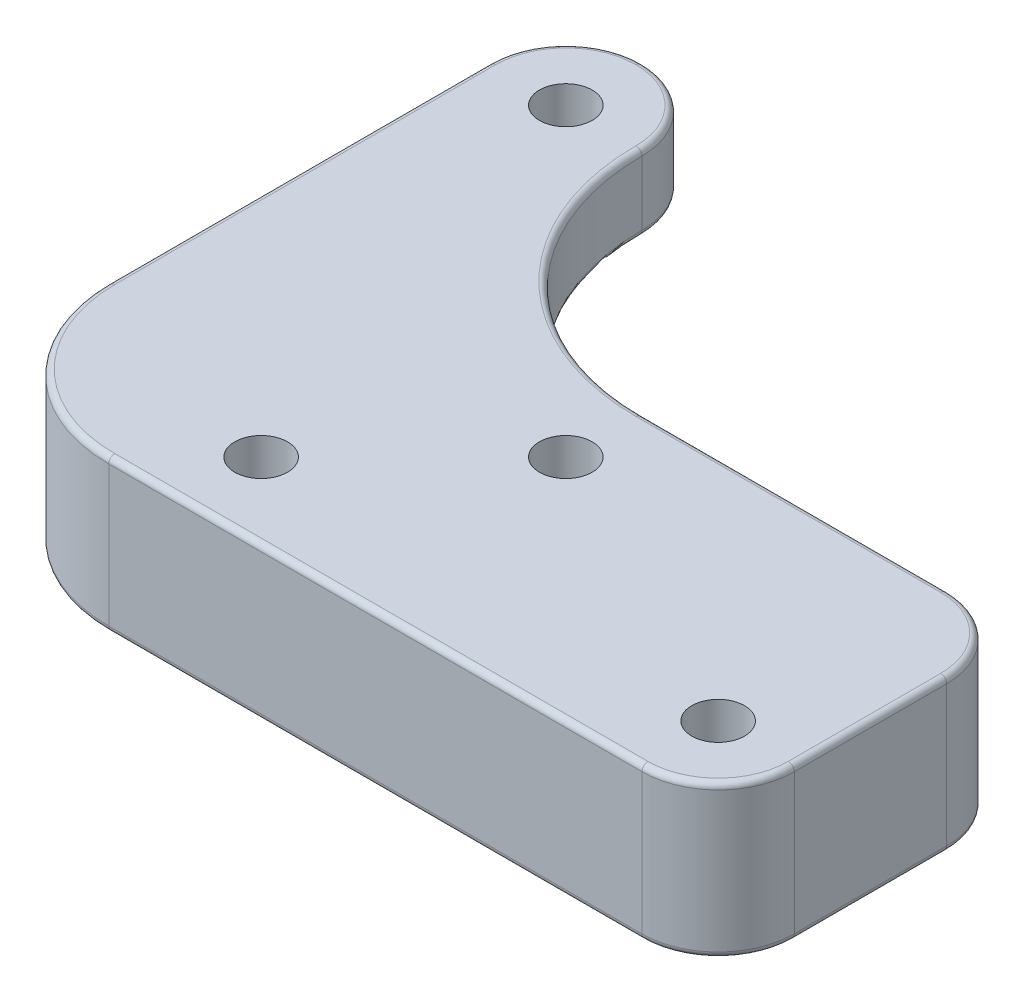
SolidWorks part; units mm, degrees
ref_plane "Front Plane" through (0, 0, 0) normal (0, 0, 1) x (1, 0, 0)
ref_plane "Top Plane" through (0, 0, 0) normal (0, 1, 0) x (1, 0, 0)
ref_plane "Right Plane" through (0, 0, 0) normal (1, 0, 0) x (0, 0, -1)
sketch "Sketch1" plane through (0, 0, 0) normal (0, 1, 0) x (1, 0, 0)
  line L0 (0, 0) -> (0, -50.8)
  line L2 (0, -50.8) -> (63.5, -50.8)
  line L3 (63.5, -50.8) -> (63.5, -25.4)
  line L4 (63.5, -25.4) -> (12.7, 0)
  line L5 (12.7, 0) -> (0, 0)
  line L6 (63.5, -25.4) -> (12.7, -25.4)
  line L7 (12.7, -25.4) -> (12.7, 0)
  circle A0 centre (19.05, -44.45) radius 2.2
  circle A1 centre (57.15, -44.45) radius 2.2
  circle A2 centre (31.75, -31.75) radius 2.2
  circle A3 centre (6.35, -6.35) radius 2.2
  point P14 (6.35, 0)
  point P15 (16.1819, -44.45)
  dimension "D1" = 4.4
  dimension "D2" = 25.4
  dimension "D3" = 12.7
  dimension "D4" = 25.4
  dimension "D5" = 63.5
  dimension "D6" = 6.35
  dimension "D7" = 6.35
  dimension "D8" = 6.35
  dimension "D9" = 12.7
  dimension "D10" = 12.7
  dimension "D11" = 12.7
extrude "Boss-Extrude1" add sketch "Sketch1" along normal blind 6.35 contours L6 L7 L5 L0 L2 L3 A3 A2 A1 A0
fillet "Fillet3" radius 19.05 1 edges at (12.7, 3.175, 25.4)
fillet "Fillet4" radius 6.35 2 edges at (0, 3.175, 0) (12.7, 3.175, 0)
fillet "Fillet5" radius 6.35 2 edges at (63.5, 3.175, 50.8) (63.5, 3.175, 25.4)
fillet "Fillet10" radius 12.7 1 edges at (0, 3.175, 50.8)
sketch "Sketch3" plane through (0, 0, 0) normal (0, -1, 0) x (1, 0, 0)
  line L0 (31.75, 25.4) -> (0, 25.4)
  line L4 (57.15, 50.8) -> (12.7, 50.8)
  line L5 (0, 38.1) -> (0, 6.35)
  line L6 (31.75, 25.4) -> (57.15, 25.4)
  line L7 (63.5, 31.75) -> (63.5, 44.45)
  line L8 (57.15, 50.8) -> (12.7, 50.8)
  line L9 (0, 38.1) -> (0, 6.35)
  line L10 (31.75, 25.4) -> (57.15, 25.4)
  line L11 (63.5, 31.75) -> (63.5, 44.45)
  circle A0 centre (57.15, 44.45) radius 2.2 construction
  circle A1 centre (19.05, 44.45) radius 2.2 construction
  circle A2 centre (31.75, 31.75) radius 2.2 construction
  circle A3 centre (57.15, 44.45) radius 2.2
  circle A4 centre (19.05, 44.45) radius 2.2
  circle A5 centre (31.75, 31.75) radius 2.2
  arc A7 (0, 6.35) -> (6.35, 0) centre (6.35, 6.35) ccw
  arc A8 (6.35, 0) -> (12.7, 6.35) centre (6.35, 6.35) ccw
  arc A9 (31.75, 25.4) -> (12.7, 6.35) centre (31.75, 6.35) ccw
  arc A10 (57.15, 25.4) -> (63.5, 31.75) centre (57.15, 31.75) ccw
  arc A11 (63.5, 44.45) -> (57.15, 50.8) centre (57.15, 44.45) ccw
  arc A13 (0, 6.35) -> (6.35, 0) centre (6.35, 6.35) ccw
  arc A14 (6.35, 0) -> (12.7, 6.35) centre (6.35, 6.35) ccw
  arc A15 (31.75, 25.4) -> (12.7, 6.35) centre (31.75, 6.35) ccw
  arc A16 (57.15, 25.4) -> (63.5, 31.75) centre (57.15, 31.75) ccw
  arc A17 (63.5, 44.45) -> (57.15, 50.8) centre (57.15, 44.45) ccw
  arc A23 (12.7, 50.8) -> (0, 38.1) centre (12.7, 38.1) ccw
  arc A24 (12.7, 50.8) -> (0, 38.1) centre (12.7, 38.1) ccw
  point P3 (0, 0)
  dimension "D1" = 0
extrude "Boss-Extrude3" add sketch "Sketch3" along normal blind 6.35
fillet "Fillet6" radius 12.7 1 edges at (0, -3.175, 25.4)
fillet "Fillet8" radius 3.175 2 edges at (3.7197, 0, 29.1197) (22.225, 0, 25.4)
fillet "Fillet9" radius 0.5 23 edges at (3.7197, -6.35, 29.1197) (0, -0.705, 32.4994) (24.0128, -0.3946, 23.758) (14.9645, 0, 15.3583) (18.2796, 6.35, 19.8204) (0, 0, 17.4625) (1.8599, 0, 1.8599) (10.8401, 0, 1.8599) (0, 6.35, 22.225) (1.8599, 6.35, 1.8599) (10.8401, 6.35, 1.8599) (63.5, 6.35, 38.1) (44.45, 6.35, 25.4) (61.6401, 6.35, 27.2599) (61.6401, 6.35, 48.9401) (34.925, 6.35, 50.8) (3.7197, 6.35, 47.0803) (34.925, -6.35, 25.4) (61.6401, -6.35, 27.2599) (63.5, -6.35, 38.1) (61.6401, -6.35, 48.9401) (34.925, -6.35, 50.8) (3.7197, -6.35, 47.0803)
